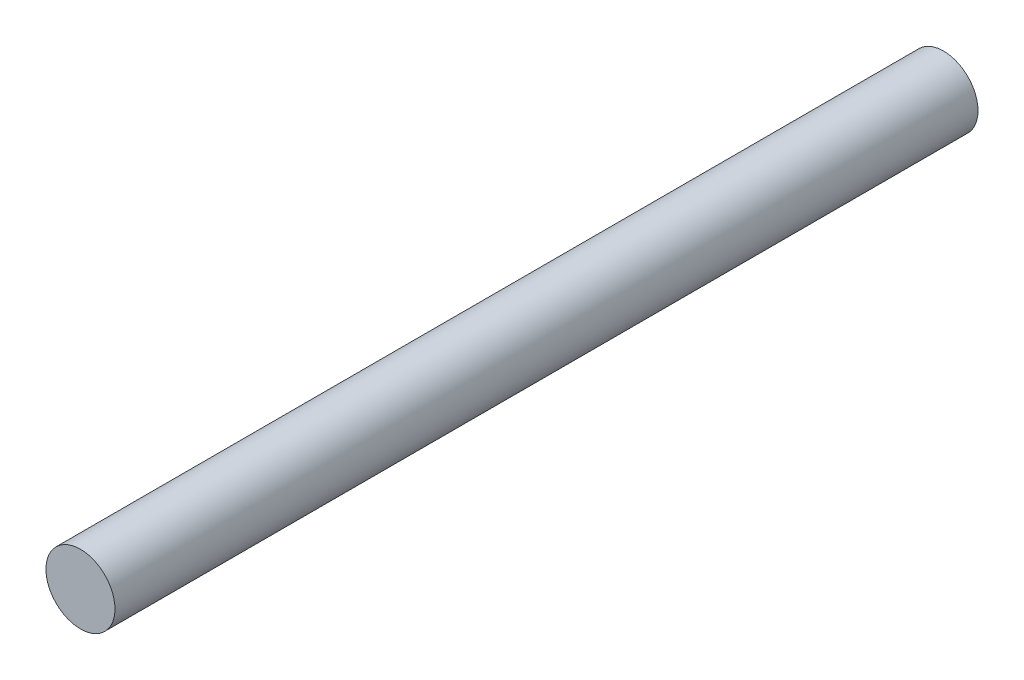
SolidWorks part; units mm, degrees
ref_plane "正面" through (0, 0, 0) normal (0, 0, 1) x (1, 0, 0)
ref_plane "平面" through (0, 0, 0) normal (0, 1, 0) x (1, 0, 0)
ref_plane "右側面" through (0, 0, 0) normal (1, 0, 0) x (0, 0, -1)
sketch "ｽｹｯﾁ1" plane through (0, 0, 0) normal (0, 0, 1) x (1, 0, 0)
  circle A0 centre (0, 0) radius 10
  dimension "D1" = 20
extrude "ﾎﾞｽ - 押し出し1" add sketch "ｽｹｯﾁ1" along normal blind 250
